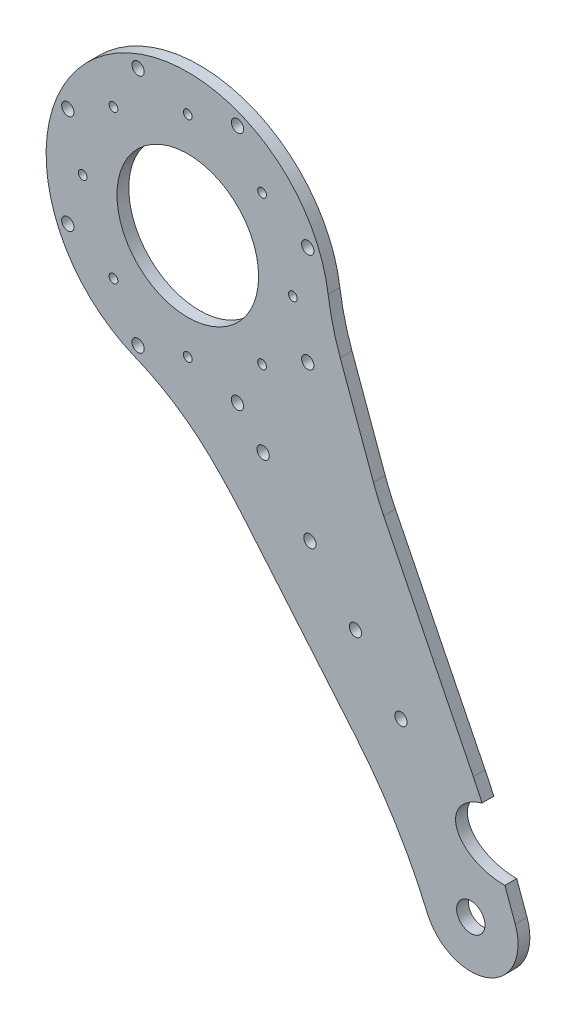
SolidWorks part; units mm, degrees
ref_plane "前视基准面" through (0, 0, 0) normal (0, 0, 1) x (1, 0, 0)
ref_plane "上视基准面" through (0, 0, 0) normal (0, 1, 0) x (1, 0, 0)
ref_plane "右视基准面" through (0, 0, 0) normal (1, 0, 0) x (0, 0, -1)
other "Configuration Table"
sketch "草图1" plane through (0, 0, 0) normal (0, 0, 1) x (1, 0, 0)
  line L0 (60, 0) -> (80.5212, -56.3816)
  line L1 (60, 0) -> (0, 0) construction
  line L2 (0, 0) -> (-56.3816, -20.5212) construction
  line L3 (-56.3816, -20.5212) -> (12.5624, -78.3721)
  line L4 (12.5624, -78.3721) -> (80.5212, -56.3816)
  line L5 (80.5212, -56.3816) -> (113.0212, -112.6732)
  line L6 (12.5624, -78.3721) -> (92.7533, -173.9399)
  line L7 (113.0212, -112.6732) -> (138.6727, -183.1502)
  line L8 (101.085, -196.831) -> (138.6727, -183.1502) construction
  line L9 (101.085, -196.831) -> (92.7533, -173.9399)
  line L10 (125.847, -147.9117) -> (80.5212, -56.3816)
  circle A0 centre (0, 0) radius 30
  circle A1 centre (0, 0) radius 60
  circle A2 centre (119.8789, -189.9906) radius 6
  circle A3 centre (119.8789, -189.9906) radius 20
  dimension "D1" = 60
  dimension "D2" = 120
  dimension "D9" = 65
  dimension "D11" = 12
  dimension "D12" = 40
  dimension "D3" = 160
  dimension "D4" = 110
  dimension "D5" = 60
  dimension "D6" = 60
  dimension "D7" = 90
  dimension "D8" = 170
  dimension "D10" = 190
  dimension "D13" = 170
  dimension "D15" = 75
  dimension "D16" = 90
extrude "凸台-拉伸1" add sketch "草图1" along normal blind 5 contours A1 L3 A0 | A1 L3 L4 L0 | A3 L7 L5 L4 L6 L9 | A3 A2 | A1 | A0 region at (37.4764, -44.6626, 0) region at (44.9639, -51.0795, 0) region at (78.2512, -115.7548, 0) region at (139.0179, -186.6158, 0)
sketch "草图2" plane through (0, 0, 5) normal (0, 0, 1) x (1, 0, 0)
  line L0 (0, 60) -> (0, 0) construction
  line L1 (-60, 0) -> (60, 0) construction
  line L6 (-10.4189, -59.0885) -> (12.5624, -78.3721)
  line L7 (12.5624, -78.3721) -> (92.7533, -173.9399)
  line L8 (92.7533, -173.9399) -> (101.085, -196.831)
  line L9 (138.6727, -183.1502) -> (125.847, -147.9117)
  line L10 (125.847, -147.9117) -> (80.5212, -56.3816)
  line L11 (80.5212, -56.3816) -> (60, 0)
  line L12 (-10.4189, -59.0885) -> (12.5624, -78.3721)
  line L13 (12.5624, -78.3721) -> (92.7533, -173.9399)
  line L14 (92.7533, -173.9399) -> (101.085, -196.831)
  line L15 (138.6727, -183.1502) -> (125.847, -147.9117)
  line L16 (125.847, -147.9117) -> (80.5212, -56.3816)
  line L17 (80.5212, -56.3816) -> (60, 0)
  circle A0 centre (0, 44.5) radius 1.85
  circle A1 centre (31.4663, 31.4663) radius 1.85
  arc A2 (60, 0) -> (-10.4189, -59.0885) centre (0, 0) ccw
  arc A3 (101.085, -196.831) -> (138.6727, -183.1502) centre (119.8789, -189.9906) ccw
  arc A4 (60, 0) -> (-10.4189, -59.0885) centre (0, 0) ccw
  arc A5 (101.085, -196.831) -> (138.6727, -183.1502) centre (119.8789, -189.9906) ccw
  circle A6 centre (44.5, 0) radius 1.85
  circle A7 centre (31.4663, -31.4663) radius 1.85
  circle A8 centre (0, -44.5) radius 1.85
  circle A9 centre (-31.4663, -31.4663) radius 1.85
  circle A10 centre (-44.5, 0) radius 1.85
  circle A11 centre (-31.4663, 31.4663) radius 1.85
  circle A12 centre (42.5, 0) radius 1.6
  circle A13 centre (-42.5, 0) radius 1.85
  point P30 (0, 0)
  dimension "D2" = 3.7
  dimension "D3" = 44.5
  dimension "D5" = 3.7
  dimension "D6" = 3.2
  dimension "D7" = 42.5
  dimension "D8" = 42.5
  dimension "D1" = 0
  dimension "D4" = 8
extrude "切除-拉伸1" cut sketch "草图2" against normal blind 10 contours A0 | A1 | A6 A12 | A6 A12 | A7 | A8 | A10 A13 | A10 A13 | A11 | A11 | A9 region at (0, 44.5, 5) region at (31.4663, 31.4663, 5) region at (43.3633, 0, 5) region at (42.028, 0, 5) region at (31.4663, -31.4663, 5) region at (0, -44.5, 5) region at (-43.5, 0, 5) region at (-41.9688, 0, 5) region at (-31.4663, 31.4663, 5)
sketch "草图3" plane through (0, 0, 5) normal (0, 0, 1) x (1, 0, 0)
  line L0 (0, 0) -> (0, 60) construction
  line L1 (0, 0) -> (31.4663, 31.4663) construction
  line L2 (0, 0) -> (22.961, 55.4328) construction
  line L6 (-10.4189, -59.0885) -> (12.5624, -78.3721)
  line L7 (12.5624, -78.3721) -> (92.7533, -173.9399)
  line L8 (92.7533, -173.9399) -> (101.085, -196.831)
  line L9 (138.6727, -183.1502) -> (125.847, -147.9117)
  line L10 (125.847, -147.9117) -> (80.5212, -56.3816)
  line L11 (80.5212, -56.3816) -> (60, 0)
  line L12 (-10.4189, -59.0885) -> (12.5624, -78.3721)
  line L13 (12.5624, -78.3721) -> (92.7533, -173.9399)
  line L14 (92.7533, -173.9399) -> (101.085, -196.831)
  line L15 (138.6727, -183.1502) -> (125.847, -147.9117)
  line L16 (125.847, -147.9117) -> (80.5212, -56.3816)
  line L17 (80.5212, -56.3816) -> (60, 0)
  circle A0 centre (21.0476, 50.8134) radius 2.6
  circle A1 centre (50.8134, 21.0476) radius 2.6
  arc A2 (60, 0) -> (-10.4189, -59.0885) centre (0, 0) ccw
  arc A3 (101.085, -196.831) -> (138.6727, -183.1502) centre (119.8789, -189.9906) ccw
  arc A4 (60, 0) -> (-10.4189, -59.0885) centre (0, 0) ccw
  arc A5 (101.085, -196.831) -> (138.6727, -183.1502) centre (119.8789, -189.9906) ccw
  circle A6 centre (50.8134, -21.0476) radius 2.6
  circle A7 centre (21.0476, -50.8134) radius 2.6
  circle A8 centre (-21.0476, -50.8134) radius 2.6
  circle A9 centre (-50.8134, -21.0476) radius 2.6
  circle A10 centre (-50.8134, 21.0476) radius 2.6
  circle A11 centre (-21.0476, 50.8134) radius 2.6
  point P33 (0, 0)
  dimension "D3" = 5.2
  dimension "D4" = 55
  dimension "D2" = 22.5
  dimension "D1" = 0
  dimension "D5" = 8
extrude "切除-拉伸2" cut sketch "草图3" against normal blind 10 contours A10 | A9 | A8 | A7 | A6 | A1 | A0 | A11
fillet "圆角1" radius 200 1 edges at (125.847, -147.9117, 2.5)
fillet "圆角2" radius 200 1 edges at (92.7533, -173.9399, 2.5)
fillet "圆角3" radius 200 1 edges at (12.5624, -78.3721, 2.5)
fillet "圆角5" radius 100 3 edges at (80.5212, -56.3816, 2.5) (60, 0, 2.5) (-10.4189, -59.0885, 2.5)
sketch "草图4" plane through (0, 0, 5) normal (0, 0, 1) x (1, 0, 0)
  line L5 (138.6727, -183.1502) -> (129.6382, -158.328)
  line L6 (120.9279, -137.9781) -> (82.9808, -61.3483)
  line L7 (78.6256, -51.1734) -> (64.5536, -12.5109)
  line L8 (23.8098, -91.7761) -> (70.6774, -147.6308)
  line L9 (42.9609, -75.7064) -> (89.8285, -131.5612)
  line L10 (138.6727, -183.1502) -> (129.6382, -158.328)
  line L11 (120.9279, -137.9781) -> (82.9808, -61.3483)
  line L12 (78.6256, -51.1734) -> (64.5536, -12.5109)
  line L13 (23.8098, -91.7761) -> (70.6774, -147.6308)
  line L15 (89.8877, -131.6317) -> (89.8877, -131.6317)
  line L16 (89.8877, -131.6317) -> (60.5772, -72.4426)
  line L17 (55.1333, -59.7239) -> (41.0613, -21.0614)
  circle A0 centre (31.9151, -63.6228) radius 2.6
  circle A1 centre (51.7254, -86.1517) radius 2.6
  circle A2 centre (63.0234, -24.2033) radius 2.6
  circle A3 centre (71.0091, -109.133) radius 2.6
  circle A4 centre (50.8134, -21.0476) radius 2.6 construction
  circle A5 centre (50.8134, -21.0476) radius 2.6
  circle A7 centre (90.2927, -132.1143) radius 2.6
  arc A8 (129.6382, -158.328) -> (120.9279, -137.9781) centre (-58.3003, -226.732) ccw
  arc A9 (78.6256, -51.1734) -> (82.9808, -61.3483) centre (172.5949, -16.9714) ccw
  arc A10 (59.4461, 8.1342) -> (64.5536, -12.5109) centre (158.5229, 21.6911) ccw
  arc A11 (59.4461, 8.1342) -> (-22.5076, -55.6184) centre (0, 0) ccw
  arc A12 (9.3586, -76.2979) -> (-22.5076, -55.6184) centre (-60.0203, -148.3158) ccw
  arc A13 (23.8098, -91.7761) -> (9.3586, -76.2979) centre (-129.3991, -220.3337) ccw
  arc A14 (101.4779, -197.8267) -> (70.6774, -147.6308) centre (-82.5315, -276.1884) ccw
  arc A15 (101.4779, -197.8267) -> (138.6727, -183.1502) centre (119.8789, -189.9906) ccw
  arc A16 (129.6382, -158.328) -> (120.9279, -137.9781) centre (-58.3003, -226.732) ccw
  arc A17 (78.6256, -51.1734) -> (82.9808, -61.3483) centre (172.5949, -16.9714) ccw
  arc A18 (59.4461, 8.1342) -> (64.5536, -12.5109) centre (158.5229, 21.6911) ccw
  arc A19 (59.4461, 8.1342) -> (-22.5076, -55.6184) centre (0, 0) ccw
  arc A20 (9.3586, -76.2979) -> (-22.5076, -55.6184) centre (-60.0203, -148.3158) ccw
  arc A21 (23.8098, -91.7761) -> (9.3586, -76.2979) centre (-129.3991, -220.3337) ccw
  arc A22 (101.4779, -197.8267) -> (70.6774, -147.6308) centre (-82.5315, -276.1884) ccw
  arc A23 (101.4779, -197.8267) -> (138.6727, -183.1502) centre (119.8789, -189.9906) ccw
  arc A38 (89.8877, -131.6317) -> (89.8285, -131.5612) centre (-82.5315, -276.1884) ccw
  arc A39 (89.8877, -131.6317) -> (89.8877, -131.6317) centre (89.8877, -131.6317) ccw
  arc A40 (89.8877, -131.6317) -> (89.8877, -131.6317) centre (89.8877, -131.6317) ccw
  arc A41 (55.1333, -59.7239) -> (60.5772, -72.4426) centre (172.5949, -16.9714) ccw
  arc A42 (34.6769, 4.7449) -> (41.0613, -21.0614) centre (158.5229, 21.6911) ccw
  arc A43 (34.6769, 4.7449) -> (-13.1294, -32.4441) centre (0, 0) ccw
  arc A44 (26.7033, -58.2934) -> (-13.1294, -32.4441) centre (-60.0203, -148.3158) ccw
  arc A45 (42.9609, -75.7064) -> (26.7033, -58.2934) centre (-129.3991, -220.3337) ccw
  dimension "D2" = 5.2
  dimension "D3" = 5.2
  dimension "D4" = 5.2
  dimension "D5" = 5.2
  dimension "D7" = 30
  dimension "D8" = 30
  dimension "D9" = 30
  dimension "D10" = 65
  dimension "D13" = 5.2
  dimension "D1" = 0
  dimension "D6" = 25
extrude "切除-拉伸3" cut sketch "草图4" against normal blind 10 contours A3 | A7 | A0 | A1
sketch "草图5" plane through (0, 0, 5) normal (0, 0, 1) x (1, 0, 0)
  ellipse E0 centre (133.0183, -157.9676) end of major axis (152.6156, -159.0188) minor radius 13.1666
extrude "切除-拉伸4" cut sketch "草图5" against normal blind 10 contours E0
sketch "草图6" plane through (0, 0, 5) normal (0, 0, 1) x (1, 0, 0)
  line L6 (-10.4189, -59.0885) -> (12.5624, -78.3721)
  line L7 (12.5624, -78.3721) -> (92.7533, -173.9399)
  line L8 (92.7533, -173.9399) -> (101.085, -196.831)
  line L9 (138.6727, -183.1502) -> (125.847, -147.9117)
  line L10 (125.847, -147.9117) -> (80.5212, -56.3816)
  line L11 (80.5212, -56.3816) -> (60, 0)
  line L12 (-10.4189, -59.0885) -> (12.5624, -78.3721)
  line L13 (12.5624, -78.3721) -> (92.7533, -173.9399)
  line L14 (92.7533, -173.9399) -> (101.085, -196.831)
  line L15 (138.6727, -183.1502) -> (125.847, -147.9117)
  line L16 (125.847, -147.9117) -> (80.5212, -56.3816)
  line L17 (80.5212, -56.3816) -> (60, 0)
  circle A1 centre (42.5, 0) radius 1.6
  circle A2 centre (42.5, 0) radius 1.6
  circle A3 centre (0, 44.5) radius 1.85
  circle A4 centre (0, 44.5) radius 1.85
  circle A5 centre (-31.4663, 31.4663) radius 1.85
  arc A6 (101.085, -196.831) -> (138.6727, -183.1502) centre (119.8789, -189.9906) ccw
  arc A7 (60, 0) -> (-10.4189, -59.0885) centre (0, 0) ccw
  arc A8 (101.085, -196.831) -> (138.6727, -183.1502) centre (119.8789, -189.9906) ccw
  arc A9 (60, 0) -> (-10.4189, -59.0885) centre (0, 0) ccw
  circle A10 centre (-31.4663, 31.4663) radius 1.85
  circle A11 centre (-44.5, 0) radius 1.85
  circle A12 centre (-44.5, 0) radius 1.85
  circle A13 centre (-31.4663, -31.4663) radius 1.85
  circle A14 centre (-31.4663, -31.4663) radius 1.85
  circle A15 centre (0, -44.5) radius 1.85
  circle A16 centre (0, -44.5) radius 1.85
  circle A17 centre (31.4663, -31.4663) radius 1.85
  circle A18 centre (31.4663, -31.4663) radius 1.85
  circle A19 centre (44.5, 0) radius 1.85
  circle A20 centre (44.5, 0) radius 1.85
  circle A21 centre (31.4663, 31.4663) radius 1.85
  circle A22 centre (31.4663, 31.4663) radius 1.85
  circle A23 centre (-42.5, 0) radius 1.85
  circle A24 centre (-42.5, 0) radius 1.85
  circle M46 centre (42.5, 0) radius 1.6
  circle M49 centre (-42.5, 0) radius 1.85
  dimension "D1" = 0
  dimension "D2" = 0
  dimension "D3" = 0
  dimension "D4" = 0
  dimension "D5" = 0
  dimension "D6" = 0
  dimension "D7" = 0
  dimension "D8" = 0
  dimension "D9" = 0
  dimension "D10" = 0
  dimension "D11" = 0
extrude "凸台-拉伸2" add sketch "草图6" against normal through all contours A12 M49 | A12 M49 | A2 A20 | A20 M46 region at (43.3633, 0, 5) region at (42.028, 0, 5) region at (-43.5, 0, 5) region at (-41.9688, 0, 5)
sketch "草图7" plane through (0, 0, 5) normal (0, 0, 1) x (1, 0, 0)
  line L4 (120.9279, -137.9781) -> (82.9808, -61.3483)
  line L5 (78.6256, -51.1734) -> (64.5536, -12.5109)
  line L6 (23.8098, -91.7761) -> (70.6774, -147.6308)
  line L7 (138.6727, -183.1502) -> (134.3065, -171.1541)
  line L8 (120.9279, -137.9781) -> (82.9808, -61.3483)
  line L9 (78.6256, -51.1734) -> (64.5536, -12.5109)
  line L10 (23.8098, -91.7761) -> (70.6774, -147.6308)
  line L11 (138.6727, -183.1502) -> (134.3065, -171.1541)
  line L14 (-10.4189, -59.0885) -> (12.5624, -78.3721)
  line L15 (12.5624, -78.3721) -> (92.7533, -173.9399)
  line L16 (92.7533, -173.9399) -> (101.085, -196.831)
  line L17 (138.6727, -183.1502) -> (125.847, -147.9117)
  line L18 (125.847, -147.9117) -> (80.5212, -56.3816)
  line L19 (80.5212, -56.3816) -> (60, 0)
  line L20 (-10.4189, -59.0885) -> (12.5624, -78.3721)
  line L21 (12.5624, -78.3721) -> (92.7533, -173.9399)
  line L22 (92.7533, -173.9399) -> (101.085, -196.831)
  line L23 (138.6727, -183.1502) -> (125.847, -147.9117)
  line L24 (125.847, -147.9117) -> (80.5212, -56.3816)
  line L25 (80.5212, -56.3816) -> (60, 0)
  circle A1 centre (42.5, 0) radius 1.6
  circle A2 centre (42.5, 0) radius 1.6
  circle A3 centre (0, 44.5) radius 1.85
  circle A4 centre (0, 44.5) radius 1.85
  circle A5 centre (-31.4663, 31.4663) radius 1.85
  arc A6 (101.085, -196.831) -> (138.6727, -183.1502) centre (119.8789, -189.9906) ccw
  arc A7 (60, 0) -> (-10.4189, -59.0885) centre (0, 0) ccw
  arc A8 (124.6011, -145.8182) -> (120.9279, -137.9781) centre (-58.3003, -226.732) ccw
  arc A9 (78.6256, -51.1734) -> (82.9808, -61.3483) centre (172.5949, -16.9714) ccw
  arc A10 (59.4461, 8.1342) -> (64.5536, -12.5109) centre (158.5229, 21.6911) ccw
  arc A11 (59.4461, 8.1342) -> (-22.5076, -55.6184) centre (0, 0) ccw
  arc A12 (9.3586, -76.2979) -> (-22.5076, -55.6184) centre (-60.0203, -148.3158) ccw
  arc A13 (23.8098, -91.7761) -> (9.3586, -76.2979) centre (-129.3991, -220.3337) ccw
  arc A14 (101.4779, -197.8267) -> (70.6774, -147.6308) centre (-82.5315, -276.1884) ccw
  arc A15 (101.4779, -197.8267) -> (138.6727, -183.1502) centre (119.8789, -189.9906) ccw
  arc A16 (124.6011, -145.8182) -> (120.9279, -137.9781) centre (-58.3003, -226.732) ccw
  arc A17 (78.6256, -51.1734) -> (82.9808, -61.3483) centre (172.5949, -16.9714) ccw
  arc A18 (59.4461, 8.1342) -> (64.5536, -12.5109) centre (158.5229, 21.6911) ccw
  arc A19 (59.4461, 8.1342) -> (-22.5076, -55.6184) centre (0, 0) ccw
  arc A20 (9.3586, -76.2979) -> (-22.5076, -55.6184) centre (-60.0203, -148.3158) ccw
  arc A21 (23.8098, -91.7761) -> (9.3586, -76.2979) centre (-129.3991, -220.3337) ccw
  arc A22 (101.4779, -197.8267) -> (70.6774, -147.6308) centre (-82.5315, -276.1884) ccw
  arc A23 (101.4779, -197.8267) -> (138.6727, -183.1502) centre (119.8789, -189.9906) ccw
  arc A24 (101.085, -196.831) -> (138.6727, -183.1502) centre (119.8789, -189.9906) ccw
  arc A25 (60, 0) -> (-10.4189, -59.0885) centre (0, 0) ccw
  circle A26 centre (-31.4663, 31.4663) radius 1.85
  circle A27 centre (-44.5, 0) radius 1.85
  circle A28 centre (-44.5, 0) radius 1.85
  circle A29 centre (-31.4663, -31.4663) radius 1.85
  circle A30 centre (-31.4663, -31.4663) radius 1.85
  circle A31 centre (0, -44.5) radius 1.85
  circle A32 centre (0, -44.5) radius 1.85
  circle A33 centre (31.4663, -31.4663) radius 1.85
  circle A34 centre (31.4663, -31.4663) radius 1.85
  circle A35 centre (44.5, 0) radius 1.85
  circle A36 centre (44.5, 0) radius 1.85
  circle A37 centre (31.4663, 31.4663) radius 1.85
  circle A38 centre (31.4663, 31.4663) radius 1.85
  circle A39 centre (-42.5, 0) radius 1.85
  circle A40 centre (-42.5, 0) radius 1.85
  ellipse E1 centre (133.0183, -157.9676) end of major axis (152.6156, -159.0188) minor radius 13.1666 (124.6011, -145.8182) -> (134.3065, -171.1541) ccw
  ellipse E2 centre (133.0183, -157.9676) end of major axis (152.6156, -159.0188) minor radius 13.1666 (124.6011, -145.8182) -> (134.3065, -171.1541) ccw
  dimension "D1" = 0
  dimension "D2" = 0
  dimension "D3" = 0
  dimension "D4" = 0
  dimension "D5" = 0
  dimension "D6" = 0
  dimension "D7" = 0
  dimension "D8" = 0
  dimension "D9" = 0
  dimension "D10" = 0
  dimension "D11" = 0
  dimension "D12" = 0
extrude "切除-拉伸5" cut sketch "草图7" against normal blind 10 contours A40 A28 | A28 A40 | A2 A36 | A2 A36 region at (43.3633, 0, 5) region at (44.9086, 0, 5) region at (-43.5, 0, 5) region at (-45.0312, 0, 5)
